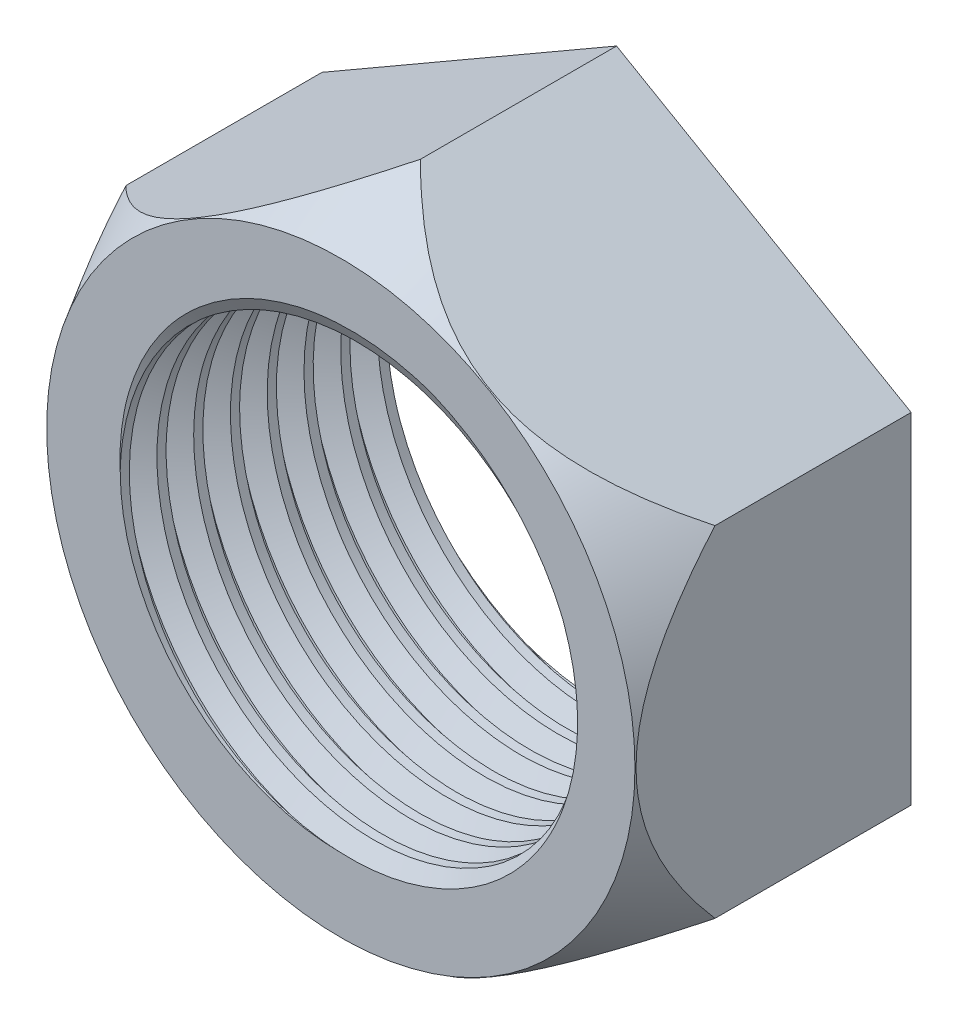
SolidWorks part; units mm, degrees
material "AISI 304"
ref_plane "Front Plane" through (0, 0, 0) normal (0, 0, 1) x (1, 0, 0)
ref_plane "Top Plane" through (0, 0, 0) normal (0, 1, 0) x (1, 0, 0)
ref_plane "Right Plane" through (0, 0, 0) normal (1, 0, 0) x (0, 0, -1)
sketch "Sketch2" plane through (0, 0, 0) normal (0, 0, 1) x (1, 0, 0)
  line L1 (0, -18.5) -> (16.0215, -9.25)
  line L2 (16.0215, -9.25) -> (16.0215, 9.25)
  line L3 (16.0215, 9.25) -> (0, 18.5)
  line L4 (0, 18.5) -> (-16.0215, 9.25)
  line L5 (-16.0215, 9.25) -> (-16.0215, -9.25)
  line L6 (-16.0215, -9.25) -> (0, -18.5)
  circle A0 centre (0, 0) radius 16.0215 construction
  dimension "D1" = 37
extrude "Boss-Extrude1" add sketch "Sketch2" along normal mid plane 15
sketch "Sketch3" plane through (0, 0, 7.5) normal (0, 0, 1) x (1, 0, 0)
  circle A0 centre (0, 0) radius 16
  dimension "D1" = 32
extrude "Cut-Extrude1" cut sketch "Sketch3" against normal blind 15 draft 30 flip side to cut
sketch "Sketch4" plane through (0, 0, 7.5) normal (0, 0, 1) x (1, 0, 0)
  circle A0 centre (0, 0) radius 12
  dimension "D1" = 24
extrude "Cut-Extrude2" cut sketch "Sketch4" against normal blind 15
thread "Thread2" pitch 2 method cut profile "Thread Profile3" start angle 0, offset 2, length 0, pitch 2, diameter 24
ref_plane "Plane3" through (12, 0, -9.5) normal (0, -1, 0) x (1, 0, 0)
sketch "Thread Profile3" plane through (12, 0, -9.5) normal (0, -1, 0) x (1, 0, 0)
  line L0 (0, 0) -> (0, 2) construction
  line L1 (0, 0) -> (1.0825, 0.625)
  line L2 (1.0825, 0.625) -> (1.0825, 0.875)
  line L3 (1.0825, 0.875) -> (0, 1.5)
  line L4 (1.0825, 0.75) -> (0, 0.75) construction
  line L11 (0, 0) -> (0, 1.5)
  point P2 (0, 0)
  dimension "Pitch" = 2
  dimension "Profile_Angle" = 60
  dimension "Profile_Land" = 0.25
  dimension "Profile_Height" = 1.0825
